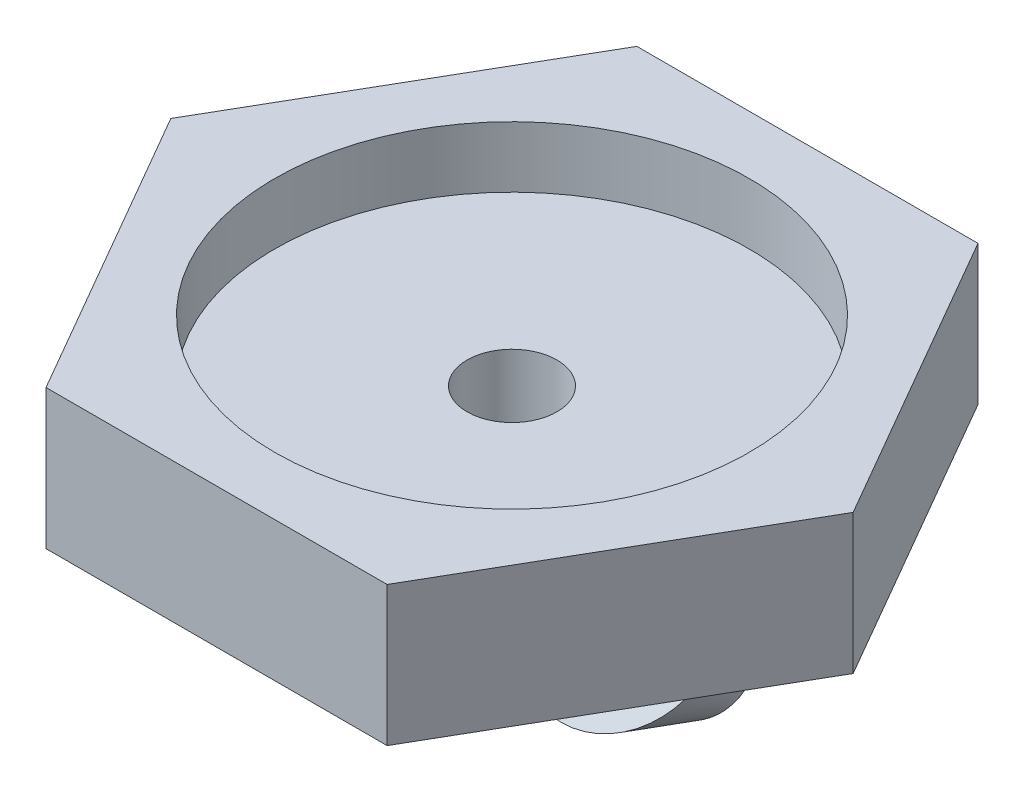
SolidWorks part; units mm, degrees
ref_plane "Front Plane" through (0, 0, 0) normal (0, 0, 1) x (1, 0, 0)
ref_plane "Top Plane" through (0, 0, 0) normal (0, 1, 0) x (1, 0, 0)
ref_plane "Right Plane" through (0, 0, 0) normal (1, 0, 0) x (0, 0, -1)
sketch "Sketch11" plane through (0, 0, 0) normal (0, 1, 0) x (1, 0, 0)
  line L7 (18.3309, 0) -> (9.1654, 15.875)
  line L8 (9.1654, 15.875) -> (-9.1654, 15.875)
  line L9 (-9.1654, 15.875) -> (-18.3309, 0)
  line L10 (-18.3309, 0) -> (-9.1654, -15.875)
  line L11 (-9.1654, -15.875) -> (9.1654, -15.875)
  line L12 (9.1654, -15.875) -> (18.3309, 0)
  circle A0 centre (0, 0) radius 15.875 construction
  dimension "D1" = 31.75
extrude "MainHolder" add sketch "Sketch11" along normal blind 7.5
sketch "Sketch12" plane through (0, 7.5, 0) normal (0, 1, 0) x (1, 0, 0)
  circle A0 centre (0, 0) radius 12.75
  dimension "D1" = 25.5
extrude "MagnetCutout" cut sketch "Sketch12" against normal blind 3.28
sketch "Sketch13" plane through (0, 4.22, 0) normal (0, 1, 0) x (1, 0, 0)
  circle A0 centre (0, 0) radius 2.415
  dimension "D1" = 4.83
extrude "MagnetHole" cut sketch "Sketch13" against normal up to next
sketch "DrainPath" plane through (0, 0, 0) normal (1, 0, 0) x (0, 0, -1)
  line L0 (0, 0) -> (0, -0.9178)
  line L1 (1.7574, -5.1604) -> (10.2426, -13.6457)
  arc A0 (1.7574, -5.1604) -> (0, -0.9178) centre (6, -0.9178) cw
  point P7 (0, -3.4031)
  dimension "D3" = 6
  dimension "D1" = 135
  dimension "D2" = 12
sketch "DrainOpening" plane through (0, 0, 0) normal (0, -1, 0) x (1, 0, 0)
  circle A0 centre (0, 0) radius 1.125
  circle A1 centre (0, 0) radius 2.415 construction
  circle A2 centre (0, 0) radius 2.415
  dimension "D1" = 2.25
sweep "Drain" add profiles "DrainOpening" path "DrainPath"
ref_axis "DrainOutAxis" through (0, -4.365, -0.9619) along (0, -0.7071, -0.7071)
ref_plane "DrainMidPlain" through (0, 0, 0) normal (-1, 0, 0) x (0, -0.7071, -0.7071)
sketch "BarbOutline" plane through (0, 0, 0) normal (-1, 0, 0) x (0, -0.7071, -0.7071)
  line L0 (16.8916, -0.0087) -> (10.8916, -0.0087)
  line L1 (10.8916, -0.0087) -> (10.8916, -2.3437)
  line L2 (10.8916, -2.3437) -> (16.8916, -0.0087)
  line L3 (4.8916, -0.0087) -> (16.8916, -0.0087) construction
  line L4 (3.7666, 2.4063) -> (18.0166, 2.4063) construction
  point P6 (0, 0)
  dimension "D1" = 6
  dimension "D2" = 4.75
revolve "Barb" add sketch "BarbOutline" angle 360 about axis through (0, -4.365, -0.9619) along (0, -0.7071, -0.7071)
equation "\"channel_diameter\"= 4mm"
equation "\"channel_length\"= 12mm"
equation "\"barb_large_diameter\"= 4.75mm"
equation "\"barb_length\"= 6mm"
equation "\"lumen_diameter\"= 2.25mm"
equation "\"magnet_holder_thickness\"= 7.5"
equation "\"magnet_diameter\"=25.4"
equation "\"magnet_holder_tolerance\"= 0.1mm"
equation "\"magnet_thickness\"= 3.18mm"
equation "\"D1@Sketch11\"=\"magnet_diameter\" * 1.25"
equation "\"D1@MainHolder\" = \"magnet_holder_thickness\""
equation "\"D1@Sketch12\"=\"magnet_diameter\" + \"magnet_holder_tolerance\""
equation "\"D1@MagnetCutout\" = \"magnet_thickness\" + \"magnet_holder_tolerance\""
equation "\"magnet_hole_small\"= 4.83mm"
equation "\"D1@Sketch13\"=\"magnet_hole_small\""
equation "\"drain_angle\"= 135"
equation "\"D1@DrainPath\" = \"drain_angle\""
equation "\"D2@DrainPath\" = \"barb_length\" * 2"
equation "\"D1@DrainOpening\" = \"lumen_diameter\""
equation "\"D1@BarbOutline\" = \"barb_length\""
equation "\"D2@BarbOutline\"=\"barb_large_diameter\""
